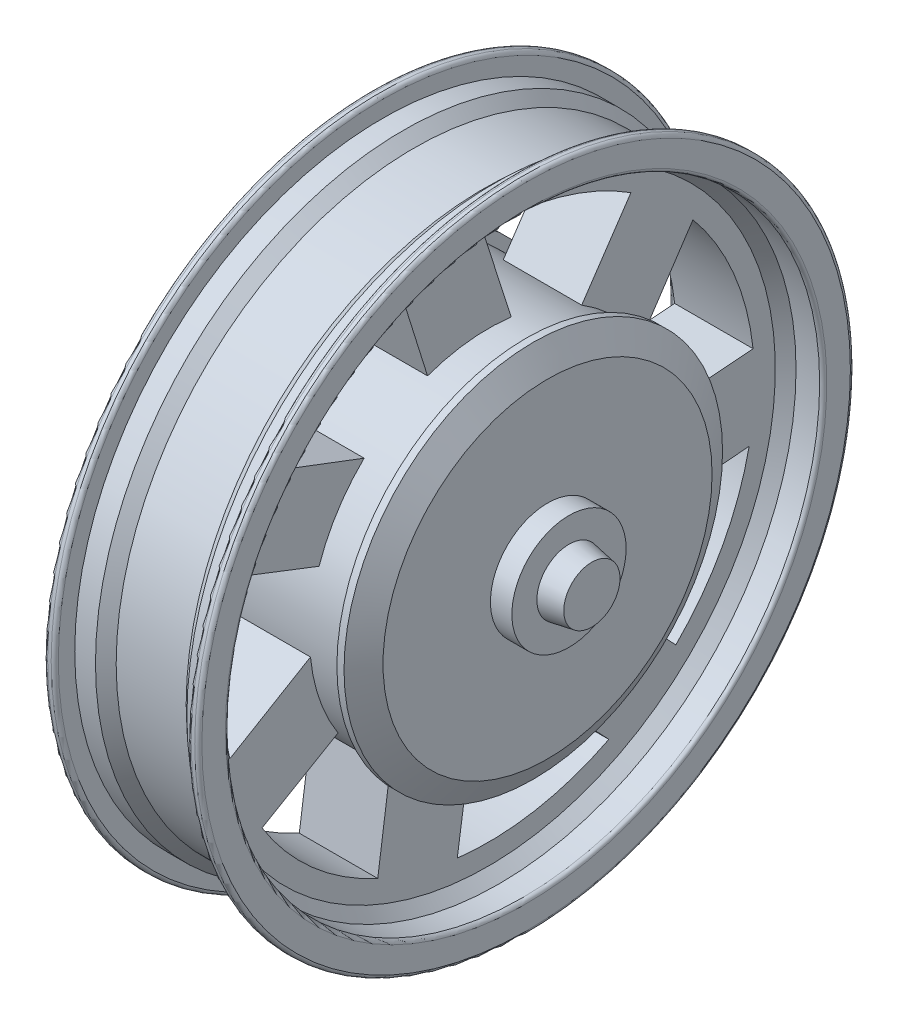
SolidWorks part; units mm, degrees
material "PBT General Purpose"
ref_plane "Front Plane" through (0, 0, 0) normal (0, 0, 1) x (1, 0, 0)
ref_plane "Top Plane" through (0, 0, 0) normal (0, 1, 0) x (1, 0, 0)
ref_plane "Right Plane" through (0, 0, 0) normal (1, 0, 0) x (0, 0, -1)
sketch "Sketch4" plane through (0, 0, 0) normal (0, 0, 1) x (1, 0, 0)
  line L0 (0, 0) -> (0, 201) construction
  line L2 (27.4562, 201) -> (34.9562, 208)
  line L3 (34.9562, 208) -> (54, 208)
  line L4 (54, 208) -> (54, 229.5)
  line L5 (54, 229.5) -> (46.5, 229.5)
  line L6 (46.5, 229.5) -> (46.5, 215.5)
  line L7 (46.5, 215.5) -> (32, 215.5)
  line L8 (32, 215.5) -> (24.5, 208.5)
  line L9 (24.5, 208.5) -> (-24.5, 208.5)
  line L10 (-54, 229.5) -> (-46.5, 229.5)
  line L11 (-54, 208) -> (-54, 229.5)
  line L12 (-46.5, 229.5) -> (-46.5, 215.5)
  line L13 (-34.9562, 208) -> (-54, 208)
  line L14 (-46.5, 215.5) -> (-32, 215.5)
  line L15 (-27.4562, 201) -> (-34.9562, 208)
  line L16 (-32, 215.5) -> (-24.5, 208.5)
  line L17 (-130.2898, 0) -> (128.111, 0) construction
  line L18 (-27.4562, 201) -> (-27.4562, 0)
  line L19 (-27.4562, 0) -> (27.4562, 0)
  line L20 (27.4562, 0) -> (27.4562, 201)
  point P23 (0, 208.5)
  dimension "D1" = 14.5
  dimension "D2" = 215.5
  dimension "D4" = 7.5
  dimension "D5" = 7.5
  dimension "D6" = 7.5
  dimension "D7" = 7.5
  dimension "D8" = 54
  dimension "D9" = 54.9124
  dimension "D10" = 229.5
revolve "Revolve1" add sketch "Sketch4" angle 360 about L17
sketch "Sketch5" plane through (27.4562, 0, 0) normal (1, 0, 0) x (0, 0, -1)
  circle A0 centre (0, 0) radius 125
  dimension "D1" = 250
extrude "Boss-Extrude2" add sketch "Sketch5" along normal up to surface (26.5438 mm away) up to face at (54, 0, 229.5)
sketch "Sketch6" plane through (-27.4562, 0, 0) normal (-1, 0, 0) x (0, 0, 1)
  circle A0 centre (0, 0) radius 125
  dimension "D1" = 250
extrude "Boss-Extrude3" add sketch "Sketch6" along normal up to surface (26.5438 mm away) up to face at (-54, 0, 208)
sketch "Sketch7" plane through (-27.4562, 0, 0) normal (-1, 0, 0) x (0, 0, 1)
  line L0 (42.4718, 117.5634) -> (60.847, 176.2949)
  line L1 (86.8778, 89.8735) -> (148.2416, 113.1666)
  line L2 (118.3955, 40.0938) -> (175.7704, 62.346)
  line L3 (124.4334, -11.8885) -> (180.9043, -45.3417)
  line L4 (105.165, -67.5672) -> (158.3351, -98.5507)
  line L5 (68.2881, -104.6983) -> (77.3424, -169.7068)
  line L6 (12.7431, -124.3488) -> (21.6703, -185.2367)
  line L7 (-39.2795, -118.6681) -> (-84.4599, -166.2792)
  line L8 (-89.2746, -87.4931) -> (-131.3127, -132.4357)
  line L9 (-117.2688, -43.2784) -> (-182.6622, -37.64)
  line L10 (-124.0667, 15.2466) -> (-185.4146, 20.0921)
  line L11 (-106.9524, 64.7008) -> (-143.3161, 119.3429)
  line L12 (-65.434, 106.5053) -> (-99.8954, 157.4902)
  line L13 (-16.0986, 123.959) -> (3.9499, 186.4582)
  circle A0 centre (0, 0) radius 125 construction
  arc A1 (86.8778, 89.8735) -> (42.4718, 117.5634) centre (0, 0) ccw
  arc A2 (148.2416, 113.1666) -> (60.847, 176.2949) centre (0, 0) ccw
  circle A3 centre (0, 0) radius 201 construction
  arc A4 (180.9043, -45.3417) -> (175.7704, 62.346) centre (0, 0) ccw
  arc A5 (124.4334, -11.8885) -> (118.3955, 40.0938) centre (0, 0) ccw
  arc A6 (77.3424, -169.7068) -> (158.3351, -98.5507) centre (0, 0) ccw
  arc A7 (68.2881, -104.6983) -> (105.165, -67.5672) centre (0, 0) ccw
  arc A8 (-84.4599, -166.2792) -> (21.6703, -185.2367) centre (0, 0) ccw
  arc A9 (-39.2795, -118.6681) -> (12.7431, -124.3488) centre (0, 0) ccw
  arc A10 (-182.6622, -37.64) -> (-131.3127, -132.4357) centre (0, 0) ccw
  arc A11 (-117.2688, -43.2784) -> (-89.2746, -87.4931) centre (0, 0) ccw
  arc A12 (-143.3161, 119.3429) -> (-185.4146, 20.0921) centre (0, 0) ccw
  arc A13 (-106.9524, 64.7008) -> (-124.0667, 15.2466) centre (0, 0) ccw
  arc A14 (3.9499, 186.4582) -> (-99.8954, 157.4902) centre (0, 0) ccw
  arc A15 (-16.0986, 123.959) -> (-65.434, 106.5053) centre (0, 0) ccw
  circle A16 centre (0, 0) radius 125 construction
  point P37 (0, 0)
  dimension "D1" = 14.5
  dimension "D2" = 7
extrude "Cut-Extrude1" cut sketch "Sketch7" against normal through all
sketch "Sketch8" plane through (54, 0, 0) normal (1, 0, 0) x (0, 0, -1)
  circle A0 centre (0, 0) radius 132.5
  dimension "D1" = 265
extrude "Boss-Extrude4" add sketch "Sketch8" along normal blind 15
sketch "Sketch9" plane through (-54, 0, 0) normal (-1, 0, 0) x (0, 0, 1)
  circle A0 centre (0, 0) radius 132.5
  dimension "D1" = 265
extrude "Boss-Extrude5" add sketch "Sketch9" along normal blind 15
chamfer "Chamfer1" distance 10 angle 60 1 edges at (69, 0, -132.5) first distance on face at (69, 0, -132.5)
chamfer "Chamfer2" distance 10 angle 60 1 edges at (-69, 0, 132.5) first distance on face at (-69, 0, 132.5)
sketch "Sketch10" plane through (69, 0, 0) normal (1, 0, 0) x (0, 0, -1)
  circle A0 centre (0, 0) radius 40
  dimension "D1" = 80
extrude "Boss-Extrude6" add sketch "Sketch10" along normal blind 15
sketch "Sketch11" plane through (-69, 0, 0) normal (-1, 0, 0) x (0, 0, 1)
  circle A0 centre (0, 0) radius 50
  dimension "D1" = 100
extrude "Boss-Extrude7" add sketch "Sketch11" along normal blind 20
sketch "Sketch12" plane through (84, 0, 0) normal (1, 0, 0) x (0, 0, -1)
  circle A0 centre (0, 0) radius 22.5
  dimension "D1" = 45
extrude "Boss-Extrude8" add sketch "Sketch12" along normal blind 16
chamfer "Chamfer3" distance 16 angle 10 1 edges at (100, 0, -22.5) first distance on face at (100, 0, -22.5)
fillet "Fillet1" radius 2.5 6 edges at (54, 0, 229.5) (-46.5, 0, 229.5) (46.5, 0, 229.5) (54, 0, 208) (-54, 0, 208) (-54, 0, 229.5)
